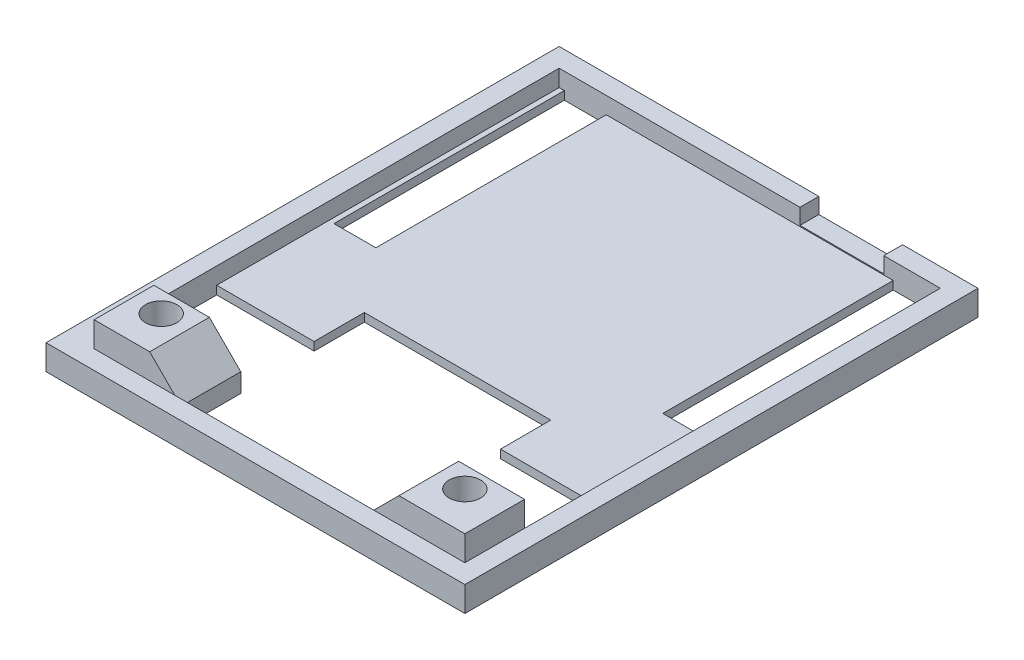
SolidWorks part; units mm, degrees
ref_plane "Front Plane" through (0, 0, 0) normal (0, 0, 1) x (1, 0, 0)
ref_plane "Top Plane" through (0, 0, 0) normal (0, 1, 0) x (1, 0, 0)
ref_plane "Right Plane" through (0, 0, 0) normal (1, 0, 0) x (0, 0, -1)
sketch "Sketch1" plane through (0, 0, 0) normal (0, 1, 0) x (1, 0, 0)
  line L1 (-20, 24.5) -> (20, 24.5)
  line L2 (-20, 24.5) -> (-20, -24.5)
  line L3 (-20, -24.5) -> (20, -24.5)
  line L4 (20, 24.5) -> (20, -24.5)
  line L5 (-20, 24.5) -> (20, -24.5) construction
  line L6 (-20, -24.5) -> (20, 24.5) construction
  point P0 (0, 0)
  dimension "D1" = 49
  dimension "D2" = 40
extrude "Boss-Extrude1" add sketch "Sketch1" along normal blind 2.4
sketch "Sketch2" plane through (0, 2.4, 0) normal (0, 1, 0) x (1, 0, 0)
  line L0 (-20, 24.5) -> (-20, -24.5) construction
  line L1 (-18.2, 22.7) -> (18.2, 22.7)
  line L2 (-18.2, 22.7) -> (-18.2, -22.7)
  line L3 (-18.2, -22.7) -> (18.2, -22.7)
  line L4 (18.2, 22.7) -> (18.2, -22.7)
  line L5 (-18.2, 22.7) -> (18.2, -22.7) construction
  line L6 (-18.2, -22.7) -> (18.2, 22.7) construction
  line L7 (20, 24.5) -> (-20, 24.5) construction
  point P0 (0, 0)
  dimension "D1" = 1.8
  dimension "D2" = 1.8
extrude "Cut-Extrude1" cut sketch "Sketch2" against normal blind 1.6
sketch "Sketch3" plane through (0, 0.8, 0) normal (0, 1, 0) x (1, 0, 0)
  line L0 (18.2, 22.7) -> (-18.2, 22.7) construction
  line L1 (-17.7, 22.7) -> (-13.7, 22.7)
  line L2 (-17.7, 22.7) -> (-17.7, 0.7)
  line L3 (-17.7, 0.7) -> (-13.7, 0.7)
  line L4 (-13.7, 22.7) -> (-13.7, 0.7)
  line L5 (-17.7, 22.7) -> (-13.7, 0.7) construction
  line L6 (-17.7, 0.7) -> (-13.7, 22.7) construction
  line L7 (-18.2, 22.7) -> (-18.2, -22.7) construction
  line L8 (0, 22.7) -> (0, -22.7) construction
  line L9 (18.2, 22.7) -> (-18.2, 22.7) construction
  line L10 (-18.2, -22.7) -> (18.2, -22.7) construction
  line L11 (17.7, 0.7) -> (13.7, 0.7)
  line L12 (13.7, 22.7) -> (13.7, 0.7)
  line L13 (17.7, 22.7) -> (13.7, 22.7)
  line L14 (17.7, 22.7) -> (17.7, 0.7)
  line L15 (0, -13.95) -> (18.2, -13.95) construction
  line L16 (-8.9, -5.2) -> (8.9, -5.2)
  line L17 (-8.9, -5.2) -> (-8.9, -22.7)
  line L18 (-8.9, -22.7) -> (8.9, -22.7)
  line L19 (8.9, -5.2) -> (8.9, -22.7)
  line L20 (-8.9, -5.2) -> (8.9, -22.7) construction
  line L21 (-8.9, -22.7) -> (8.9, -5.2) construction
  line L22 (18.2, -22.7) -> (18.2, 22.7) construction
  line L23 (18.2, -13.95) -> (-18.2, -13.95) construction
  line L24 (-18.2, 22.7) -> (-18.2, -22.7) construction
  line L25 (-18.2, -22.7) -> (18.2, -22.7) construction
  line L26 (-18.2, -10) -> (-8.9, -10)
  line L27 (-18.2, -10) -> (-18.2, -17)
  line L28 (-18.2, -17) -> (-8.9, -17)
  line L29 (-8.9, -10) -> (-8.9, -17)
  line L30 (18.2, -17) -> (8.9, -17)
  line L31 (8.9, -10) -> (8.9, -17)
  line L32 (18.2, -10) -> (8.9, -10)
  line L33 (18.2, -10) -> (18.2, -17)
  point P0 (-15.7, 11.7)
  point P19 (0, -13.95)
  line M14 (18.2, -22.7) -> (18.2, 22.7)
  line M16 (-18.2, 22.7) -> (-18.2, -22.7)
  line M17 (-18.2, -22.7) -> (18.2, -22.7)
  dimension "D1" = 22
  dimension "D2" = 4
  dimension "D3" = 0
  dimension "D4" = 0.5
  dimension "D5" = 17.5
  dimension "D6" = 17.8
  dimension "D7" = 5.7
  dimension "D8" = 4.8
extrude "Cut-Extrude2" cut sketch "Sketch3" against normal blind 1.6 contours L28 L17 L26 M16 | L19 L16 L17 M17 | L32 L19 L30 M14 | L14 L13 L12 L11 | L4 L1 L2 L3 region at (-15.7, 0.8, -11.7) region at (15.7, 0.8, -11.7) region at (0, 0.8, 13.95) region at (-13.55, 0.8, 13.5) region at (13.55, 0.8, 13.5)
sketch "Sketch4" plane through (0, 0.8, 0) normal (0, 1, 0) x (1, 0, 0)
  line L0 (0, 0) -> (0, -22.7) construction
  line L1 (-18.2, -22.7) -> (-8.9, -22.7)
  line L2 (-18.2, -22.7) -> (-18.2, -17)
  line L3 (-18.2, -17) -> (-8.9, -17)
  line L4 (-8.9, -22.7) -> (-8.9, -17)
  line L5 (-18.2, -22.7) -> (18.2, -22.7) construction
  line L6 (18.2, -17) -> (8.9, -17)
  line L7 (8.9, -22.7) -> (8.9, -17)
  line L8 (18.2, -22.7) -> (8.9, -22.7)
  line L9 (18.2, -22.7) -> (18.2, -17)
extrude "Boss-Extrude2" add sketch "Sketch4" along normal blind 4
sketch "Sketch5" plane through (0, 4.8, 0) normal (0, 1, 0) x (1, 0, 0)
  line L0 (-18.2, -22.7) -> (-8.9, -22.7) construction
  line L1 (-18.2, -17) -> (-18.2, -22.7) construction
  line L2 (0, 0) -> (0, -22.7) construction
  line L3 (-8.9, -22.7) -> (8.9, -22.7) construction
  circle A0 centre (-14.5, -19) radius 1.5
  circle A1 centre (14.5, -19) radius 1.5
  dimension "D1" = 3
  dimension "D2" = 3.7
  dimension "D3" = 3.7
extrude "Cut-Extrude3" cut sketch "Sketch5" against normal blind 5
chamfer "Chamfer1" distance 3 angle 45 2 edges at (8.9, 4.8, 19.85) (-8.9, 4.8, 19.85)
sketch "Sketch6" plane through (0, 2.4, 0) normal (0, 1, 0) x (1, 0, 0)
  line L0 (18.2, 22.7) -> (17.7, 22.7) construction
  line L1 (4.8, 22.7) -> (12.8, 22.7)
  line L2 (4.8, 22.7) -> (4.8, 24.5)
  line L3 (4.8, 24.5) -> (12.8, 24.5)
  line L4 (12.8, 22.7) -> (12.8, 24.5)
  line L5 (20, 24.5) -> (-20, 24.5) construction
  line L6 (18.2, -10) -> (18.2, 22.7) construction
  point P8 (12.8, 23.6)
  dimension "D1" = 5.4
  dimension "D2" = 8
extrude "Cut-Extrude4" cut sketch "Sketch6" against normal blind 1.5
sketch "Sketch7" plane through (0, 4.8, 0) normal (0, 1, 0) x (1, 0, 0)
  line L0 (-18.2, -22.7) -> (-9.5, -22.7) construction
  line L1 (-18.2, -17) -> (-17.2, -17)
  line L2 (-18.2, -17) -> (-18.2, -22.7)
  line L3 (-18.2, -22.7) -> (-17.2, -22.7)
  line L4 (-17.2, -17) -> (-17.2, -22.7)
  dimension "D1" = 1
extrude "Cut-Extrude5" cut sketch "Sketch7" against normal blind 2.4
